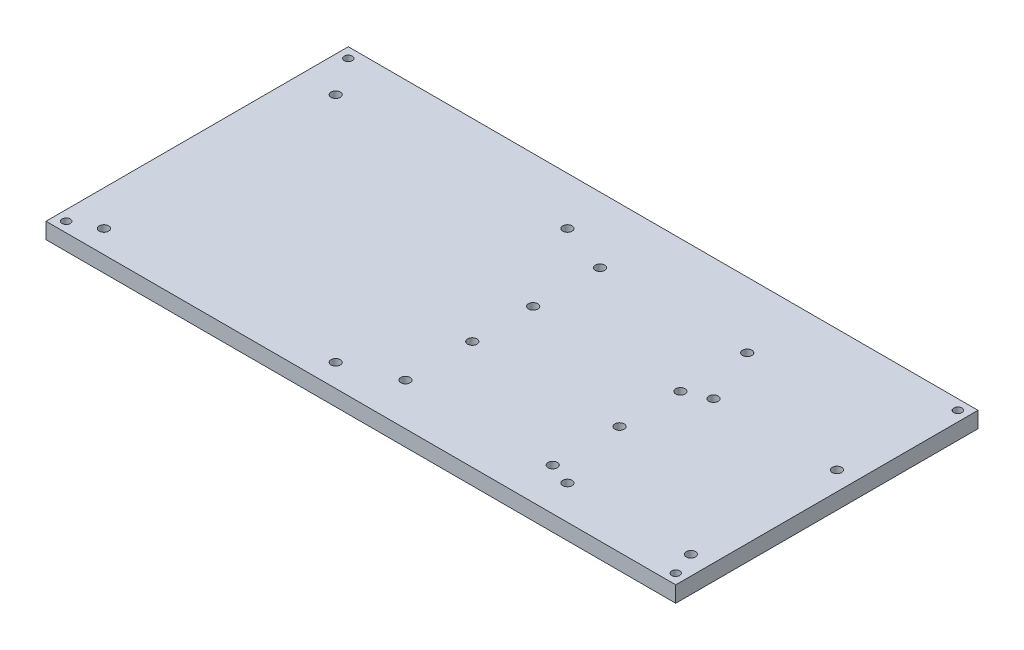
SolidWorks part; units mm, degrees
ref_plane "Front Plane" through (0, 0, 0) normal (0, 0, 1) x (1, 0, 0)
ref_plane "Top Plane" through (0, 0, 0) normal (0, 1, 0) x (1, 0, 0)
ref_plane "Right Plane" through (0, 0, 0) normal (1, 0, 0) x (0, 0, -1)
sketch "Sketch1" plane through (0, 0, 0) normal (0, 1, 0) x (1, 0, 0)
  line L1 (-125, -60) -> (125, -60)
  line L2 (-125, -60) -> (-125, 60)
  line L3 (-125, 60) -> (125, 60)
  line L4 (125, -60) -> (125, 60)
  line L5 (-125, -60) -> (125, 60) construction
  line L6 (-125, 60) -> (125, -60) construction
  point P0 (0, 0)
  dimension "D1" = 120
  dimension "D2" = 250
extrude "Boss-Extrude1" add sketch "Sketch1" along normal blind 6.35
hole_wizard "Ø3.0mm Clearance Dowel Hole2" positions "Sketch4" profile "Sketch5" hole size "Ø3.0" standard "ANSI Metric" end condition through all
sketch "Sketch4" plane through (-51.3136, 0, 70.4001) normal (0, -1, 0) x (-1, 0, 0)
  point P0 (-52.2886, 77.8401)
  point P3 (-32.3136, 111.4001)
  point P6 (-52.2886, 104.3601)
  point P9 (-52.2886, 53.6601)
  point P12 (-52.2886, 27.1401)
  point P15 (-32.3136, 19.4001)
  point P18 (59.6864, 19.4001)
  point P51 (-110.7386, 27.1401)
  point P54 (-110.7386, 53.6601)
  point P57 (-110.7386, 77.8401)
  point P60 (-110.7386, 104.3601)
  point P63 (-168.8136, 23.9001)
  point P66 (-168.8136, 81.9001)
  point P69 (-119.8136, 81.9001)
  point P72 (-119.8136, 23.9001)
  point P81 (59.6864, 111.4001)
sketch "Sketch5" plane through (0.975, 0, -7.44) normal (1, 0, 0) x (0, 0, -1)
  line L0 (0, 0) -> (0, 6.35)
  line L1 (0, 6.35) -> (1.85, 6.35)
  line L2 (1.85, 6.35) -> (1.85, 0)
  line L3 (1.85, 0) -> (0, 0)
  line L4 (0, -6.35) -> (0, 107.95) construction
  dimension "Thru Hole Dia." = 3.7
  dimension "Thru Hole Depth" = 6.35
sketch "Sketch6" plane through (0, 6.35, 0) normal (0, 1, 0) x (1, 0, 0)
  line L8 (121, -56) -> (121, 56)
  line L9 (-121, -56) -> (121, -56)
  line L10 (-121, 56) -> (-121, -56)
  line L11 (121, 56) -> (-121, 56)
  line L12 (121, -56) -> (121, 56) construction
  line L13 (-121, -56) -> (121, -56) construction
  line L14 (-121, 56) -> (-121, -56) construction
  line L15 (121, 56) -> (-121, 56) construction
  circle A0 centre (-121, 56) radius 1.6
  circle A1 centre (-121, -56) radius 1.6
  circle A2 centre (121, -56) radius 1.6
  circle A3 centre (121, 56) radius 1.6
  point P9 (0, 0)
  dimension "D2" = 3.2
  dimension "D1" = 4
extrude "Cut-Extrude1" cut sketch "Sketch6" against normal through all
